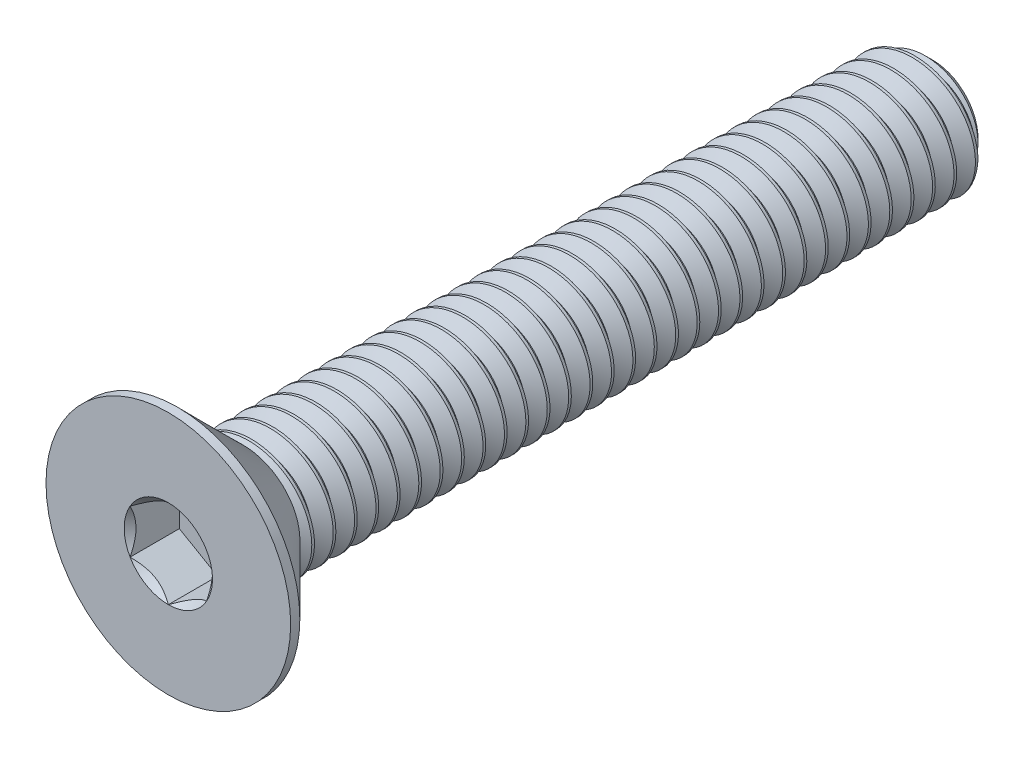
SolidWorks part; units mm, degrees
ref_plane "Front" through (0, 0, 0) normal (0, 0, 1) x (1, 0, 0)
ref_plane "Top" through (0, 0, 0) normal (0, 1, 0) x (1, 0, 0)
ref_plane "Right" through (0, 0, 0) normal (1, 0, 0) x (0, 0, -1)
sketch "Sketch1" plane through (0, 0, 0) normal (1, 0, 0) x (0, 0, -1)
  line L0 (0, 4) -> (0.3, 4) construction
  line L1 (0.3, 4) -> (2.3, 2) construction
  line L2 (0, 2) -> (25, 2)
  line L3 (25, 2) -> (25, 0)
  line L4 (25, 0) -> (0, 0)
  line L5 (0, 0) -> (0, 4) construction
  line L6 (0, 4) -> (0, -4) construction
  line L7 (25, 2) -> (25, -2) construction
  line L8 (0, -4) -> (0.3, -4) construction
  line L9 (0.3, -4) -> (2.3, -2) construction
  line L11 (0, 2) -> (0, 0)
  line L12 (2.3, 2) -> (2.3, 0) construction
revolve "Revolve1" add sketch "Sketch1" angle 360 mid plane about L4
sketch "Sketch3" plane through (0, 0, -25) normal (0, 0, -1) x (-1, 0, 0)
  circle A0 centre (0, 0) radius 2
curve "Helix/Spiral1" pitch 0.7 height 25 turns 35.7143
sketch "Sketch2" plane through (0, 0, 0) normal (1, 0, 0) x (0, 0, -1)
  line L0 (25, 2) -> (25.6125, 2)
  line L1 (25.6125, 2) -> (25.35, 1.5453)
  line L2 (25.35, 1.5453) -> (25.2625, 1.5453)
  line L3 (25.2625, 1.5453) -> (25, 2)
  line L4 (25.1313, 1.7727) -> (25.4813, 1.7727) construction
  dimension "D1" = 60
  dimension "D2" = 0.0875
  dimension "D3" = 0.35
chamfer "Chamfer1" distance 0.525 angle 45 1 edges at (0, 2, -25)
sweep "Cut-Sweep1" cut profiles "Sketch2" path "Helix/Spiral1"
sketch "Sketch7" plane through (0, 0, 0) normal (1, 0, 0) x (0, 0, -1)
  line L0 (0, 4) -> (0.3, 4) construction
  line L1 (0.3, 4) -> (2.3, 2) construction
  line L2 (0, 4) -> (0.3, 4)
  line L3 (0.3, 4) -> (2.3, 2)
  line L4 (2.3, 2) -> (2.3, 0) construction
  line L5 (2.3, 2) -> (2.3, 0)
  line L7 (0, 0) -> (0, 4) construction
  line L8 (0, 0) -> (0, 4)
  line L9 (0, 0) -> (2.3, 0)
  line L10 (4.4, 0) -> (-4.4, 0) construction
revolve "Revolve2" add sketch "Sketch7" angle 360 mid plane about L9
ref_plane "Plane1" through (0, 0, -2.3) normal (0, 0, 1) x (1, 0, 0)
sketch "Sketch8" plane through (0, 0, -2.3) normal (0, 0, 1) x (1, 0, 0)
  circle A0 centre (0, 0) radius 2
extrude "Boss-Extrude1" add sketch "Sketch8" against normal through all draft 45
sketch "Sketch5" plane through (0, 0, 0) normal (0, 0, 1) x (1, 0, 0)
  line L1 (1.25, -0.7217) -> (1.25, 0.7217)
  line L2 (1.25, 0.7217) -> (0, 1.4434)
  line L3 (0, 1.4434) -> (-1.25, 0.7217)
  line L4 (-1.25, 0.7217) -> (-1.25, -0.7217)
  line L5 (-1.25, -0.7217) -> (0, -1.4434)
  line L6 (0, -1.4434) -> (1.25, -0.7217)
  circle A0 centre (0, 0) radius 1.25 construction
  dimension "Hex" = 2.5
extrude "Cut-Extrude2" cut sketch "Sketch5" against normal blind 1.61
sketch "Sketch6" plane through (0, 0, 0) normal (0, 0, 1) x (1, 0, 0)
  circle A0 centre (0, 0) radius 1.4434
extrude "Cut-Extrude3" cut sketch "Sketch6" against normal blind 1.61 draft 45
sketch "Sketch9" [suppressed] plane through (0, 0, -5.5) normal (0, 0, 1) x (1, 0, 0)
  circle A1 centre (0, 0) radius 5
  circle A2 centre (0, 0) radius 5
  point P0 (0, 5)
  dimension "D1" = 0
extrude "Boss-Extrude2" [suppressed] add sketch "Sketch9" against normal offset from surface (18.5 mm away) 26
fillet "Fillet1" [suppressed] radius 0.4
sketch "Sketch10" plane through (0, 0, 0) normal (1, 0, 0) x (0, 0, -1)
  line L0 (25, 2) -> (25, -2) construction
  point P0 (23.95, -2)
  dimension "D1" = 1.05
equation "\"D3@Helix/Spiral1\" = \"Lg@Sketch1\""
equation "\"D2@Sketch2\" = \"D4@Helix/Spiral1\" * .125"
equation "\"D3@Sketch2\" = \"D4@Helix/Spiral1\" * .5"
equation "\"D1@Chamfer1\" = \"D4@Helix/Spiral1\" * .75"
equation "\"D1@Cut-Extrude2\" = \"Head Ht@Sketch1\" * .7"
equation "\"D1@Sketch10\" = \"D4@Helix/Spiral1\" * 1.5"
equation "\"D1@Cut-Extrude3\" = \"D1@Cut-Extrude2\""
equation "\"D1@Fillet1\" = \"Dia@Sketch1\" * .1"
